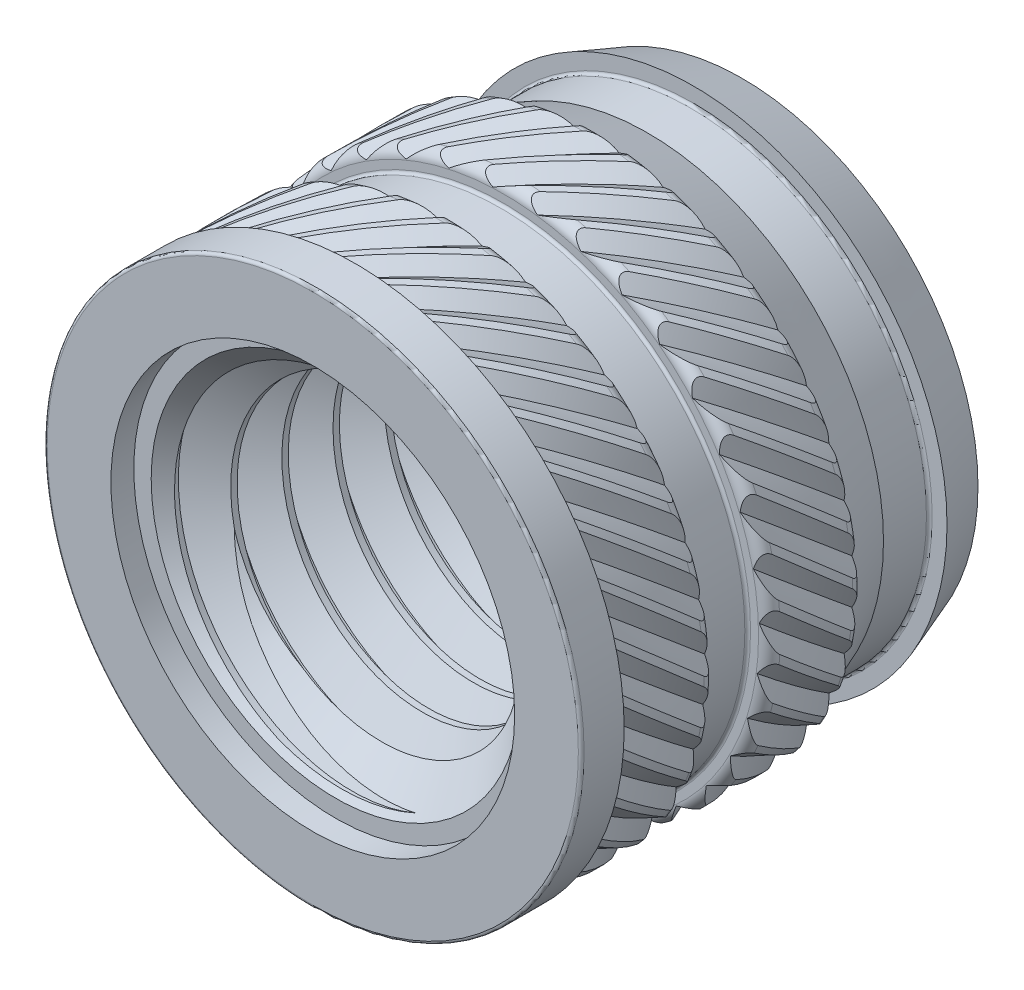
SolidWorks part; units mm, degrees
ref_plane "Front Plane" through (0, 0, 0) normal (0, 0, 1) x (1, 0, 0)
ref_plane "Top Plane" through (0, 0, 0) normal (0, 1, 0) x (1, 0, 0)
ref_plane "Right Plane" through (0, 0, 0) normal (1, 0, 0) x (0, 0, -1)
sketch "Sketch1" plane through (0, 0, 0) normal (1, 0, 0) x (0, 0, -1)
  line L0 (-3.81, 0) -> (3.81, 0) construction
  line L1 (-3.81, 3.175) -> (-3.81, 4.7625)
  line L2 (-3.81, 4.7625) -> (-3.048, 4.7625)
  line L3 (-3.048, 4.7625) -> (-3.048, 4.7149)
  line L4 (-3.048, 4.7149) -> (-1.3915, 4.7149)
  line L5 (-1.3915, 4.7149) -> (-1.3915, 4.3295)
  line L6 (-1.3915, 4.3295) -> (-0.4236, 4.3295)
  line L7 (-0.4236, 4.3295) -> (-0.4236, 4.7149)
  line L11 (2.9462, 4.1814) -> (2.1334, 4.1814)
  line L14 (2.9462, 4.1814) -> (2.9462, 4.4958)
  line L15 (2.9462, 4.4958) -> (3.81, 4.1814)
  line L16 (3.81, 4.1814) -> (3.81, 3.175)
  line L17 (-3.81, 4.4958) -> (3.81, 4.4958) construction
  line L18 (3.81, 0) -> (3.81, 4.4958) construction
  line L19 (-3.81, 0) -> (-3.81, 4.7625) construction
  line L20 (-0.4236, 4.7149) -> (1.2329, 4.7149)
  line L21 (-3.81, 3.175) -> (3.81, 3.175)
  line L22 (-3.81, -4.4958) -> (3.81, -4.4958) construction
  line L23 (-4.6604, 3.2732) -> (-4.2069, 2.4876) construction
  line L24 (1.2329, 4.7149) -> (1.2329, 4.5372)
  line L25 (-4.2069, 2.4876) -> (-3.7533, 3.2732) construction
  line L26 (-3.7533, 3.2732) -> (-4.6604, 3.2732) construction
  line L27 (-4.6037, 3.175) -> (-3.81, 3.175) construction
  line L28 (-4.2069, 3.2732) -> (-4.2069, 3.175) construction
  line L29 (-4.2069, 3.175) -> (-4.2069, 2.5858) construction
  line L30 (-4.2069, 2.5858) -> (-4.2069, 2.4876) construction
  line L31 (-4.2636, 2.5858) -> (-4.1502, 2.5858)
  line L32 (-4.6321, 3.2241) -> (-3.7817, 3.2241)
  line L33 (-4.1502, 2.5858) -> (-3.7817, 3.2241)
  line L34 (-4.2636, 2.5858) -> (-4.6321, 3.2241)
  line L35 (-3.81, 4.4323) -> (3.81, 4.4323) construction
  line L36 (-3.81, -4.4323) -> (3.81, -4.4323) construction
  line L37 (1.2329, 4.5372) -> (2.1334, 4.1814)
  point P27 (-0.4236, 4.5222)
  point P36 (-4.2069, 3.2241)
  dimension "Installed Length" = 7.62
  dimension "Dia A" = 9.525
  dimension "Dia B" = 8.9916
  dimension "Thread Size" = 6.35
  dimension "D6" = 20
  dimension "D8" = 1.6565
  dimension "Thread Pitch" = 0.9071
  dimension "D2" = 0.1134
  dimension "For Maximum Hole Diameter" = 8.8646
  dimension "D3" = 8.3628
  dimension "D1" = 0.762
  dimension "D7" = 0.8128
  dimension "D9" = 9.4297
  dimension "Knurling Length" = 4.2809
  dimension "D4" = 8.6591
  dimension "D5" = 0.1777
ref_plane "Plane1" through (0, 0, 3.048) normal (0, 0, 1) x (1, 0, 0)
sketch "Sketch2" plane through (0, 0, 0) normal (0, 0, 1) x (1, 0, 0)
  line L0 (0, 0) -> (0, 4.7149) construction
  line L1 (-0.3289, 4.7034) -> (0, 4.5372)
  line L2 (0.3289, 4.7034) -> (0, 4.5372)
  line L3 (-0.3289, 4.7034) -> (0, 0) construction
  line L4 (0.3289, 4.7034) -> (0, 0) construction
  line L5 (0, 0) -> (-0.6154, 4.6745) construction
  line L6 (0, 0) -> (0.6154, 4.6745) construction
  line L7 (0, 0) -> (3.3339, 3.3339) construction
  line L8 (0, 0) -> (0, -3.2732) construction
  line L9 (0, 0) -> (1.6366, -2.8347) construction
  circle A0 centre (0, 0) radius 4.5372 construction
  circle A1 centre (0, 0) radius 4.7149 construction
  arc A2 (-0.3289, 4.7034) -> (0.3289, 4.7034) centre (0, 0) cw
  circle A3 centre (0, 0) radius 3.2732
  dimension "Knurl Angle" = 8
  dimension "Pattern Angle" = 15
  dimension "Helix Angle" = 45
  dimension "D1" = 30
sketch "Sketch3" plane through (0, 0, 0) normal (1, 0, 0) x (0, 0, -1)
  line L0 (-3.81, 3.175) -> (-3.81, 4.7625) construction
  line L1 (-3.81, 4.7625) -> (-3.048, 4.7625) construction
  line L2 (-3.048, 4.7625) -> (-3.048, 4.7149) construction
  line L3 (-3.048, 4.7149) -> (-1.3915, 4.7149) construction
  line L4 (-1.3915, 4.7149) -> (-1.3915, 4.3295) construction
  line L5 (-1.3915, 4.3295) -> (-0.4236, 4.3295) construction
  line L6 (-0.4236, 4.3295) -> (-0.4236, 4.7149) construction
  line L7 (1.2329, 4.7149) -> (1.2329, 4.5372) construction
  line L9 (2.9462, 4.1814) -> (2.1334, 4.1814) construction
  line L10 (1.2329, 4.5372) -> (2.1334, 4.1814) construction
  line L11 (1.2329, 4.7149) -> (1.2329, 4.5372) construction
  line L12 (1.2329, 4.5372) -> (2.1334, 4.1814)
  line L13 (2.9462, 4.1814) -> (2.9462, 4.4958) construction
  line L14 (2.9462, 4.4958) -> (3.81, 4.1814) construction
  line L15 (3.81, 4.1814) -> (3.81, 3.175) construction
  line L16 (-3.81, 3.175) -> (3.81, 3.175) construction
  line L17 (-3.81, 3.5814) -> (-3.81, 4.7117)
  line L18 (-3.7592, 4.7625) -> (-3.048, 4.7625)
  line L19 (-3.048, 4.7625) -> (-3.048, 4.7149)
  line L20 (-3.048, 4.7149) -> (-1.5841, 4.7149)
  line L21 (-1.3915, 4.5222) -> (-1.3915, 4.3803)
  line L22 (-1.3407, 4.3295) -> (-0.4744, 4.3295)
  line L23 (-0.4236, 4.3803) -> (-0.4236, 4.5222)
  line L26 (2.8954, 4.1814) -> (2.1334, 4.1814)
  line L30 (2.9462, 4.2322) -> (2.9462, 4.4958)
  line L31 (2.9462, 4.4958) -> (3.81, 4.1814)
  line L32 (3.81, 4.1814) -> (3.81, 3.175)
  line L33 (-3.4036, 3.175) -> (3.81, 3.175)
  line L34 (-0.4236, 4.7149) -> (1.2329, 4.7149) construction
  line L35 (-0.231, 4.7149) -> (1.2329, 4.7149) construction
  line L37 (-3.81, 3.5814) -> (-3.4036, 3.5814)
  line L38 (-3.4036, 3.5814) -> (-3.4036, 3.175)
  line L39 (-1.5841, 4.7149) -> (-1.5841, 4.3295) construction
  line L40 (-0.231, 4.7149) -> (1.0552, 4.7149)
  arc A0 (-0.4744, 4.3295) -> (-0.4236, 4.3803) centre (-0.4744, 4.3803) ccw
  arc A1 (-1.3915, 4.3803) -> (-1.3407, 4.3295) centre (-1.3407, 4.3803) ccw
  arc A2 (2.8954, 4.1814) -> (2.9462, 4.2322) centre (2.8954, 4.2322) ccw
  arc A3 (-0.4236, 4.5222) -> (-0.231, 4.7149) centre (-0.231, 4.5222) cw
  arc A4 (-1.3915, 4.5222) -> (-1.5841, 4.7149) centre (-1.5841, 4.5222) ccw
  arc A5 (1.2329, 4.5372) -> (1.0552, 4.7149) centre (1.0552, 4.5372) ccw
  arc A6 (-3.81, 4.7117) -> (-3.7592, 4.7625) centre (-3.7592, 4.7117) cw
  point P14 (-3.4036, 4.7625)
  dimension "D1" = 0.0508
  dimension "D2" = 0.0508
revolve "Revolve1" add sketch "Sketch3" angle 360 about L0
sketch "Sketch4" plane through (0, 0, 3.048) normal (0, 0, 1) x (1, 0, 0)
  circle A2 centre (0, 0) radius 4.7149 construction
  circle A3 centre (0, 0) radius 4.7149
sketch "Sketch5" plane through (0, 0, 3.81) normal (0, 0, 1) x (1, 0, 0)
  circle A0 centre (0, 0) radius 3.175
curve "Helix/Spiral1" pitch 0.9071 height 9.5758 radius 3.175 centre (0, 0, 3.81) axis (0, 0, -1) start towards (0, 1, 0)
sketch "Sketch6" plane through (0, 0, 0) normal (1, 0, 0) x (0, 0, -1)
  line L0 (-4.2636, 2.5858) -> (-4.1502, 2.5858) construction
  line L1 (-4.2636, 2.5858) -> (-4.6321, 3.2241) construction
  line L2 (-4.6321, 3.2241) -> (-3.7817, 3.2241) construction
  line L3 (-4.1502, 2.5858) -> (-3.7817, 3.2241) construction
  line L4 (-4.2636, 2.5858) -> (-4.1502, 2.5858)
  line L5 (-4.2636, 2.5858) -> (-4.6321, 3.2241)
  line L6 (-4.6321, 3.2241) -> (-3.7817, 3.2241)
  line L7 (-4.1502, 2.5858) -> (-3.7817, 3.2241)
sweep "Sweep1" add profiles "Sketch6" path "Helix/Spiral1"
sketch "Sketch7" plane through (0, 0, 3.4036) normal (0, 0, 1) x (1, 0, 0)
  circle A0 centre (0, 0) radius 3.2732
extrude "Cut-Extrude1" cut sketch "Sketch7" against normal through all draft 45 and the other way through all
extrude "Cut-Extrude2" cut sketch "Sketch7<2>" against normal through all and the other way through all draft 45 from surface starting at face at (4.1814, 0, -3.81)
sketch "Sketch7<2>" plane through (0, 0, 3.4036) normal (0, 0, 1) x (1, 0, 0) same geometry as "Sketch7"
curve "Helix/Spiral2" pitch 34.2472 height 4.709 radius 4.7149 centre (0, 0, 3.048) axis (0, 0, -1) start towards (0, 1, 0)
sketch "Sketch8" plane through (0, 0, 3.048) normal (0, 0, 1) x (1, 0, 0)
  line L0 (-0.3289, 4.7034) -> (0, 4.5372) construction
  line L1 (0.3289, 4.7034) -> (0, 4.5372) construction
  line L2 (-0.3289, 4.7034) -> (0, 4.5372)
  line L3 (0.3289, 4.7034) -> (0, 4.5372)
  arc A0 (0.3289, 4.7034) -> (-0.3289, 4.7034) centre (0, 0) ccw construction
  arc A1 (0.3289, 4.7034) -> (-0.3289, 4.7034) centre (0, 0) ccw
sweep "Cut-Sweep1" cut profiles "Sketch8" path "Helix/Spiral2" align with end faces yes
pattern_circular "CirPattern1" count 36 over 360 about axis through (0, 0, 3.81) along (0, 0, -1) of "Cut-Sweep1"
equation "\"D8@Sketch1\"=\"Installed Length@Sketch1\" / 4.6"
equation "\"D4@Helix/Spiral2\" = \"Knurling Length@Sketch1\" *  ( 360 / \"Helix Angle@Sketch2\" ) "
equation "\"D3@Helix/Spiral2\" = \"Knurling Length@Sketch1\" * 1.1"
equation "\"D1@CirPattern1\" =  ( \"D3@CirPattern1\" / \"Pattern Angle@Sketch2\" )  * 1.5"
equation "\"D2@Sketch1\" = \"Thread Pitch@Sketch1\" / 8"
equation "\"D4@Helix/Spiral1\" = \"Thread Pitch@Sketch1\""
equation "\"D3@Sketch1\"=\"For Maximum Hole Diameter@Sketch1\" / 1.06"
equation "\"D1@Sketch1\"=\"Installed Length@Sketch1\" * 0.1"
equation "\"D9@Sketch1\"=\"Dia A@Sketch1\"*.99"
equation "\"D4@Sketch1\"=\"Dia A@Sketch1\" / 1.1"
equation "\"Knurling Length@Sketch1\"=\"Installed Length@Sketch1\" / 1.78"
equation "\"D5@Sketch1\"=\"Dia A@Sketch1\" / 53.6"
equation "\"D7@Sketch1\"=\"Installed Length@Sketch1\" / 9.375"
